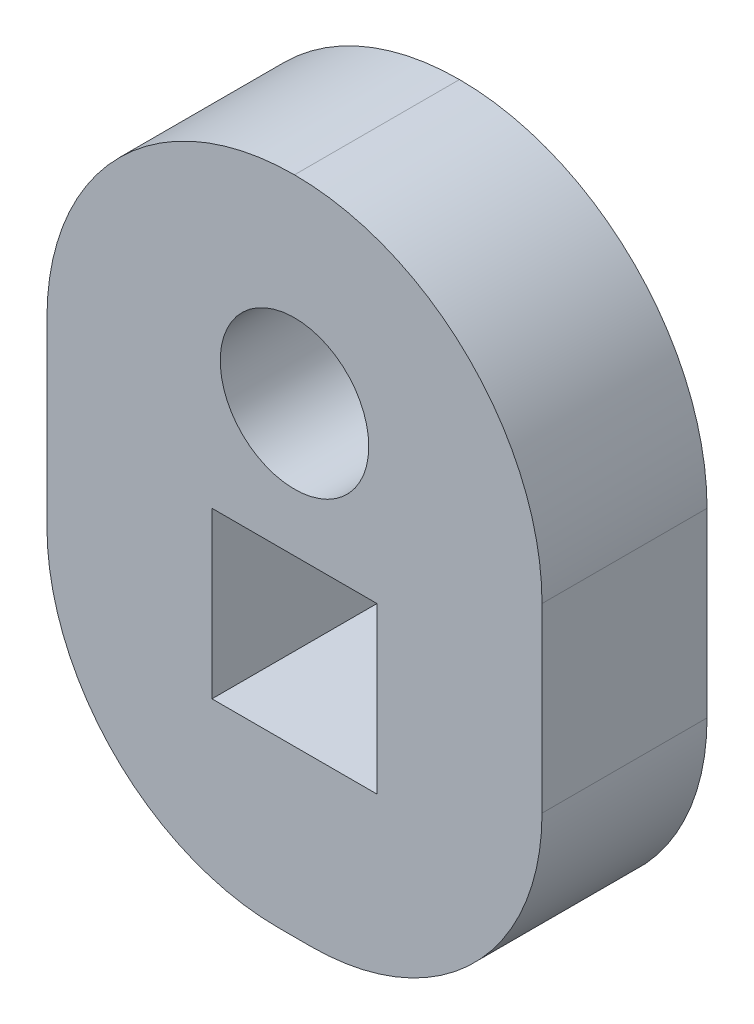
SolidWorks part; units mm, degrees
ref_plane "Plan de face" through (0, 0, 0) normal (0, 0, 1) x (1, 0, 0)
ref_plane "Plan de dessus" through (0, 0, 0) normal (0, 1, 0) x (1, 0, 0)
ref_plane "Plan de droite" through (0, 0, 0) normal (1, 0, 0) x (0, 0, -1)
sketch "Esquisse1" plane through (0, 0, 0) normal (0, 0, 1) x (1, 0, 0)
  line L1 (-52.9777, -24.3273) -> (-37.9777, -24.3273)
  line L2 (-52.9777, -24.3273) -> (-52.9777, -44.3273)
  line L3 (-52.9777, -44.3273) -> (-37.9777, -44.3273)
  line L4 (-37.9777, -24.3273) -> (-37.9777, -44.3273)
extrude "Boss.-Extru.1" add sketch "Esquisse1" along normal blind 5
sketch "Esquisse2" plane through (0, 0, 5) normal (0, 0, 1) x (1, 0, 0)
  line L0 (-52.9777, -24.3273) -> (-52.9777, -44.3273) construction
  line L1 (-47.9777, -34.3273) -> (-42.9777, -34.3273)
  line L2 (-47.9777, -34.3273) -> (-47.9777, -39.3273)
  line L3 (-47.9777, -39.3273) -> (-42.9777, -39.3273)
  line L4 (-42.9777, -34.3273) -> (-42.9777, -39.3273)
  line L5 (-37.9777, -44.3273) -> (-37.9777, -24.3273) construction
  line L6 (-52.9777, -44.3273) -> (-37.9777, -44.3273) construction
  line L7 (-37.9777, -24.3273) -> (-52.9777, -24.3273) construction
  circle A1 centre (-45.4777, -30.3273) radius 2.25
  dimension "D1" = 5
  dimension "D2" = 5
  dimension "D3" = 5
  dimension "D4" = 5
  dimension "D5" = 5
  dimension "D6" = 7.5
  dimension "D7" = 6
extrude "Enlèv. mat.-Extru.1" cut sketch "Esquisse2" against normal blind 5 contours L4 L1 L2 L3 | A1 region at (-45.4777, -36.8273, 5) region at (-45.4777, -30.3273, 5)
fillet "Congé1" radius 7.5 1 edges at (-52.9777, -24.3273, 2.5) type face fillet first side face at (-52.9777, -34.3273, 2.5) second side face at (-45.4777, -24.3273, 2.5)
fillet "Congé4" radius 7.5 1 edges at (-37.9777, -24.3273, 2.5) type face fillet first side face at (-37.9777, -34.3273, 2.5) second side face at (-41.7277, -24.3273, 2.5)
fillet "Congé5" radius 7 2 edges at (-37.9777, -44.3273, 2.5) (-52.9777, -44.3273, 2.5)
